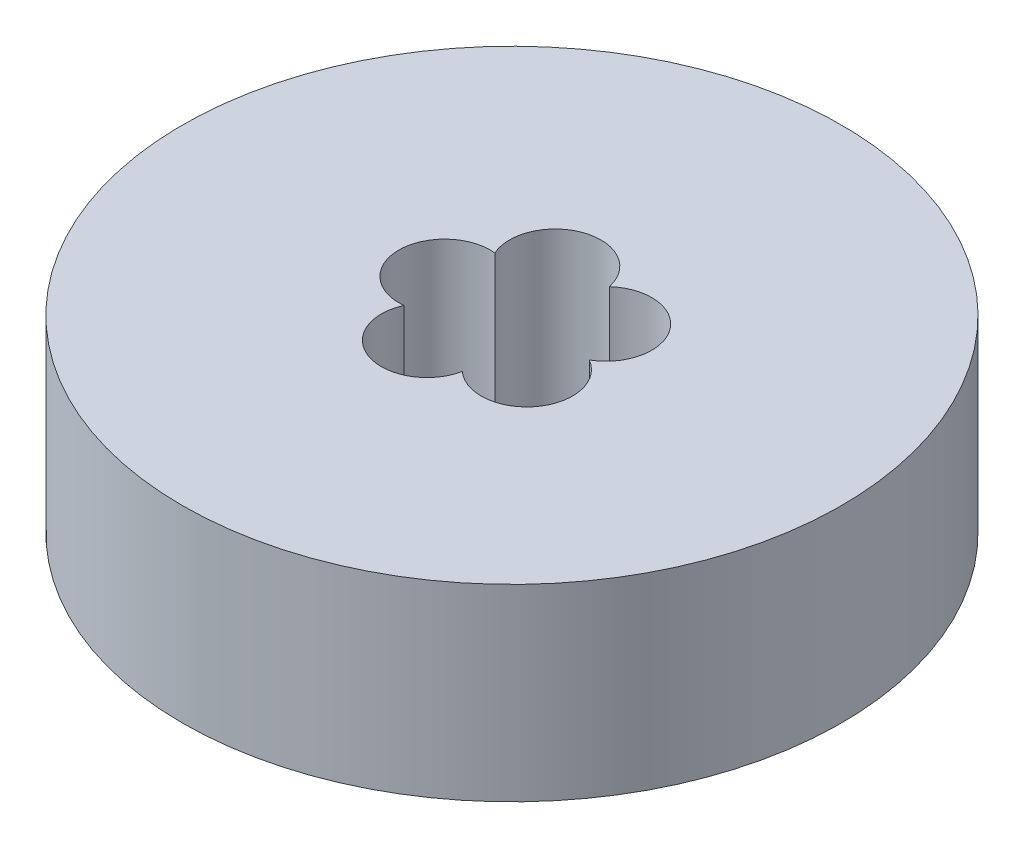
SolidWorks part; units mm, degrees
ref_plane "Front Plane" through (0, 0, 0) normal (0, 0, 1) x (1, 0, 0)
ref_plane "Top Plane" through (0, 0, 0) normal (0, 1, 0) x (1, 0, 0)
ref_plane "Right Plane" through (0, 0, 0) normal (1, 0, 0) x (0, 0, -1)
sketch "Sketch1" plane through (0, 0, 0) normal (0, 1, 0) x (1, 0, 0)
  circle A0 centre (0, 0) radius 35
  dimension "FLANGE_OD" = 70
extrude "Boss-Extrude1" add sketch "Sketch1" along normal blind 20
sketch "Sketch2" plane through (0, 0, 0) normal (0, 1, 0) x (1, 0, 0)
  circle A0 centre (0, 0) radius 7.5
  dimension "BORE_D" = 15
extrude "Cut-Extrude1" cut sketch "Sketch2" along normal through all
sketch "Sketch3" plane through (0, 20, 0) normal (0, 1, 0) x (1, 0, 0)
  circle A0 centre (0, 0) radius 7.1568 construction
  circle A1 centre (-7.1568, 0) radius 4.8552
  dimension "BOLT_D" = 9.7104
  dimension "BOLT_PCD" = 14.3135
extrude "Cut-Extrude2" cut sketch "Sketch3" against normal blind 17.0753
pattern_circular "CirPattern1" count 5 over 360 about axis through (0, 0, 0) along (0, 1, 0) of "Cut-Extrude2"
